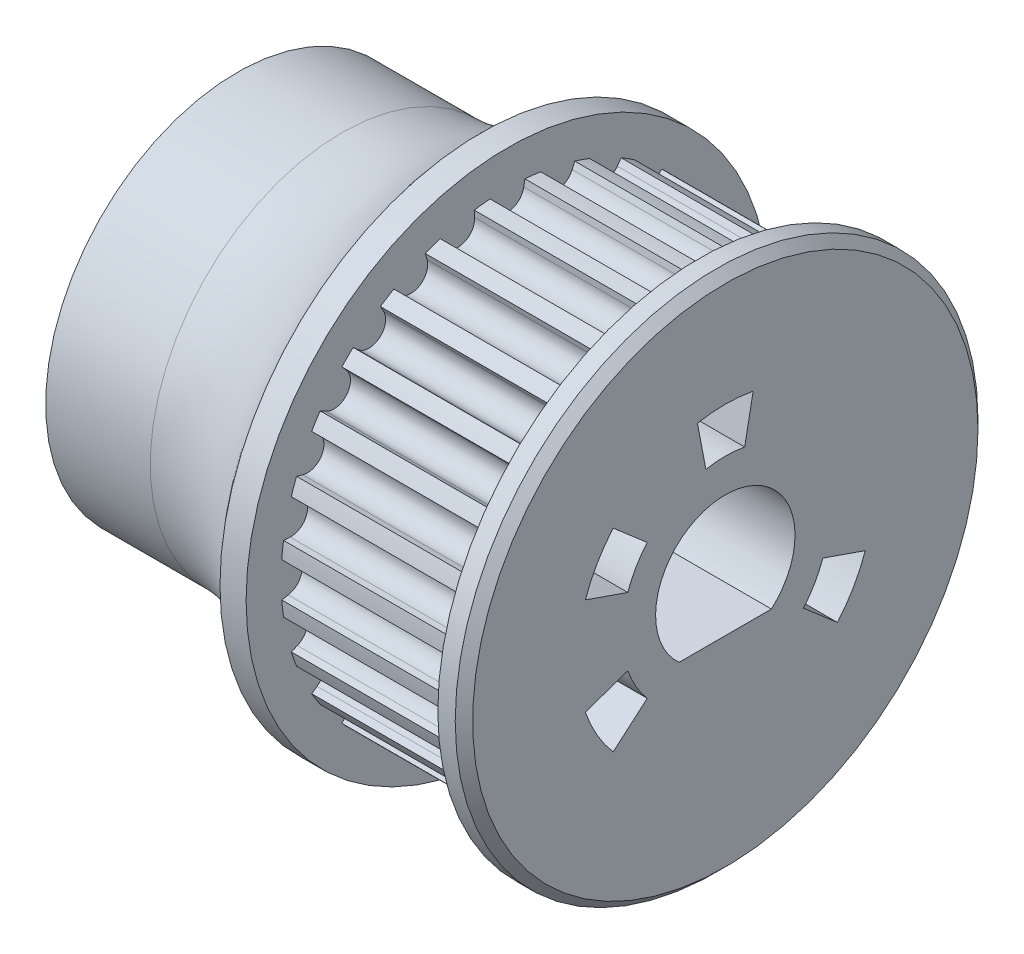
SolidWorks part; units mm, degrees
other "Markup1"
sketch "Sketch8" plane through (-10.5, -15, 15) normal (0, 0, 1) x (1, 0, 0)
material "PLA Density Only"
ref_plane "Front Plane" through (0, 0, 0) normal (0, 0, 1) x (1, 0, 0)
ref_plane "Top Plane" through (0, 0, 0) normal (0, 1, 0) x (1, 0, 0)
ref_plane "Right Plane" through (0, 0, 0) normal (1, 0, 0) x (0, 0, -1)
ref_plane "Plane1" through (-5.5, 0, 0) normal (-1, 0, 0) x (0, -1, 0)
sketch "Sketch5" plane through (0, 0, 0) normal (1, 0, 0) x (0, 0, -1)
  line L0 (1, 12.9515) -> (0.9364, 12.5797)
  line L1 (-0.9364, 12.5797) -> (-1, 12.9515)
  line L2 (-1.907, 12.8493) -> (-1.8863, 12.4727)
  line L3 (-3.7122, 12.056) -> (-3.8569, 12.4042)
  line L4 (-4.7185, 12.1027) -> (-4.6145, 11.7402)
  line L5 (-6.3018, 10.9277) -> (-6.5204, 11.235)
  line L6 (-7.2933, 10.7493) -> (-7.1112, 10.4191)
  line L7 (-8.5754, 9.2514) -> (-8.8569, 9.5024)
  line L8 (-9.5024, 8.8569) -> (-9.2514, 8.5754)
  line L9 (-10.4191, 7.1112) -> (-10.7493, 7.2933)
  line L10 (-11.235, 6.5204) -> (-10.9277, 6.3018)
  line L11 (-11.7402, 4.6145) -> (-12.1027, 4.7185)
  line L12 (-12.4042, 3.8569) -> (-12.056, 3.7122)
  line L13 (-12.4727, 1.8863) -> (-12.8493, 1.907)
  line L14 (-12.9515, 1) -> (-12.5797, 0.9364)
  line L15 (-12.5797, -0.9364) -> (-12.9515, -1)
  line L16 (-12.8493, -1.907) -> (-12.4727, -1.8863)
  line L17 (-12.056, -3.7122) -> (-12.4042, -3.8569)
  line L18 (-12.1027, -4.7185) -> (-11.7402, -4.6145)
  line L19 (-10.9277, -6.3018) -> (-11.235, -6.5204)
  line L20 (-10.7493, -7.2933) -> (-10.4191, -7.1112)
  line L21 (-9.2514, -8.5754) -> (-9.5024, -8.8569)
  line L22 (-8.8569, -9.5024) -> (-8.5754, -9.2514)
  line L23 (-7.1112, -10.4191) -> (-7.2933, -10.7493)
  line L24 (-6.5204, -11.235) -> (-6.3018, -10.9277)
  line L25 (-4.6145, -11.7402) -> (-4.7185, -12.1027)
  line L26 (-3.8569, -12.4042) -> (-3.7122, -12.056)
  line L27 (-1.8863, -12.4727) -> (-1.907, -12.8493)
  line L28 (-1, -12.9515) -> (-0.9364, -12.5797)
  line L29 (0.9364, -12.5797) -> (1, -12.9515)
  line L30 (1.907, -12.8493) -> (1.8863, -12.4727)
  line L31 (3.7122, -12.056) -> (3.8569, -12.4042)
  line L32 (4.7185, -12.1027) -> (4.6145, -11.7402)
  line L33 (6.3018, -10.9277) -> (6.5204, -11.235)
  line L34 (7.2933, -10.7493) -> (7.1112, -10.4191)
  line L35 (8.5754, -9.2514) -> (8.8569, -9.5024)
  line L36 (9.5024, -8.8569) -> (9.2514, -8.5754)
  line L37 (10.4191, -7.1112) -> (10.7493, -7.2933)
  line L38 (11.235, -6.5204) -> (10.9277, -6.3018)
  line L39 (11.7402, -4.6145) -> (12.1027, -4.7185)
  line L40 (12.4042, -3.8569) -> (12.056, -3.7122)
  line L41 (12.4727, -1.8863) -> (12.8493, -1.907)
  line L42 (12.9515, -1) -> (12.5797, -0.9364)
  line L43 (12.5797, 0.9364) -> (12.9515, 1)
  line L44 (12.8493, 1.907) -> (12.4727, 1.8863)
  line L45 (12.056, 3.7122) -> (12.4042, 3.8569)
  line L46 (12.1027, 4.7185) -> (11.7402, 4.6145)
  line L47 (10.9277, 6.3018) -> (11.235, 6.5204)
  line L48 (10.7493, 7.2933) -> (10.4191, 7.1112)
  line L49 (9.2514, 8.5754) -> (9.5024, 8.8569)
  line L50 (8.8569, 9.5024) -> (8.5754, 9.2514)
  line L51 (7.1112, 10.4191) -> (7.2933, 10.7493)
  line L52 (6.5204, 11.235) -> (6.3018, 10.9277)
  line L53 (4.6145, 11.7402) -> (4.7185, 12.1027)
  line L54 (3.8569, 12.4042) -> (3.7122, 12.056)
  line L55 (1.8863, 12.4727) -> (1.907, 12.8493)
  circle A0 centre (0, 0) radius 4
  arc A1 (0.9364, 12.5797) -> (-0.9364, 12.5797) centre (0, 12.74) cw
  arc A2 (-1, 12.9515) -> (-1.907, 12.8493) centre (0, 0) ccw
  arc A3 (-1.8863, 12.4727) -> (-3.7122, 12.056) centre (-2.8349, 12.4206) cw
  arc A4 (-3.8569, 12.4042) -> (-4.7185, 12.1027) centre (0, 0) ccw
  arc A5 (-4.6145, 11.7402) -> (-6.3018, 10.9277) centre (-5.5277, 11.4783) cw
  arc A6 (-6.5204, 11.235) -> (-7.2933, 10.7493) centre (0, 0) ccw
  arc A7 (-7.1112, 10.4191) -> (-8.5754, 9.2514) centre (-7.9433, 9.9605) cw
  arc A8 (-8.8569, 9.5024) -> (-9.5024, 8.8569) centre (0, 0) ccw
  arc A9 (-9.2514, 8.5754) -> (-10.4191, 7.1112) centre (-9.9605, 7.9433) cw
  arc A10 (-10.7493, 7.2933) -> (-11.235, 6.5204) centre (0, 0) ccw
  arc A11 (-10.9277, 6.3018) -> (-11.7402, 4.6145) centre (-11.4783, 5.5277) cw
  arc A12 (-12.1027, 4.7185) -> (-12.4042, 3.8569) centre (0, 0) ccw
  arc A13 (-12.056, 3.7122) -> (-12.4727, 1.8863) centre (-12.4206, 2.8349) cw
  arc A14 (-12.8493, 1.907) -> (-12.9515, 1) centre (0, 0) ccw
  arc A15 (-12.5797, 0.9364) -> (-12.5797, -0.9364) centre (-12.74, 0) cw
  arc A16 (-12.9515, -1) -> (-12.8493, -1.907) centre (0, 0) ccw
  arc A17 (-12.4727, -1.8863) -> (-12.056, -3.7122) centre (-12.4206, -2.8349) cw
  arc A18 (-12.4042, -3.8569) -> (-12.1027, -4.7185) centre (0, 0) ccw
  arc A19 (-11.7402, -4.6145) -> (-10.9277, -6.3018) centre (-11.4783, -5.5277) cw
  arc A20 (-11.235, -6.5204) -> (-10.7493, -7.2933) centre (0, 0) ccw
  arc A21 (-10.4191, -7.1112) -> (-9.2514, -8.5754) centre (-9.9605, -7.9433) cw
  arc A22 (-9.5024, -8.8569) -> (-8.8569, -9.5024) centre (0, 0) ccw
  arc A23 (-8.5754, -9.2514) -> (-7.1112, -10.4191) centre (-7.9433, -9.9605) cw
  arc A24 (-7.2933, -10.7493) -> (-6.5204, -11.235) centre (0, 0) ccw
  arc A25 (-6.3018, -10.9277) -> (-4.6145, -11.7402) centre (-5.5277, -11.4783) cw
  arc A26 (-4.7185, -12.1027) -> (-3.8569, -12.4042) centre (0, 0) ccw
  arc A27 (-3.7122, -12.056) -> (-1.8863, -12.4727) centre (-2.8349, -12.4206) cw
  arc A28 (-1.907, -12.8493) -> (-1, -12.9515) centre (0, 0) ccw
  arc A29 (-0.9364, -12.5797) -> (0.9364, -12.5797) centre (0, -12.74) cw
  arc A30 (1, -12.9515) -> (1.907, -12.8493) centre (0, 0) ccw
  arc A31 (1.8863, -12.4727) -> (3.7122, -12.056) centre (2.8349, -12.4206) cw
  arc A32 (3.8569, -12.4042) -> (4.7185, -12.1027) centre (0, 0) ccw
  arc A33 (4.6145, -11.7402) -> (6.3018, -10.9277) centre (5.5277, -11.4783) cw
  arc A34 (6.5204, -11.235) -> (7.2933, -10.7493) centre (0, 0) ccw
  arc A35 (7.1112, -10.4191) -> (8.5754, -9.2514) centre (7.9433, -9.9605) cw
  arc A36 (8.8569, -9.5024) -> (9.5024, -8.8569) centre (0, 0) ccw
  arc A37 (9.2514, -8.5754) -> (10.4191, -7.1112) centre (9.9605, -7.9433) cw
  arc A38 (10.7493, -7.2933) -> (11.235, -6.5204) centre (0, 0) ccw
  arc A39 (10.9277, -6.3018) -> (11.7402, -4.6145) centre (11.4783, -5.5277) cw
  arc A40 (12.1027, -4.7185) -> (12.4042, -3.8569) centre (0, 0) ccw
  arc A41 (12.056, -3.7122) -> (12.4727, -1.8863) centre (12.4206, -2.8349) cw
  arc A42 (12.8493, -1.907) -> (12.9515, -1) centre (0, 0) ccw
  arc A43 (12.5797, -0.9364) -> (12.5797, 0.9364) centre (12.74, 0) cw
  arc A44 (12.9515, 1) -> (12.8493, 1.907) centre (0, 0) ccw
  arc A45 (12.4727, 1.8863) -> (12.056, 3.7122) centre (12.4206, 2.8349) cw
  arc A46 (12.4042, 3.8569) -> (12.1027, 4.7185) centre (0, 0) ccw
  arc A47 (11.7402, 4.6145) -> (10.9277, 6.3018) centre (11.4783, 5.5277) cw
  arc A48 (11.235, 6.5204) -> (10.7493, 7.2933) centre (0, 0) ccw
  arc A49 (10.4191, 7.1112) -> (9.2514, 8.5754) centre (9.9605, 7.9433) cw
  arc A50 (9.5024, 8.8569) -> (8.8569, 9.5024) centre (0, 0) ccw
  arc A51 (8.5754, 9.2514) -> (7.1112, 10.4191) centre (7.9433, 9.9605) cw
  arc A52 (7.2933, 10.7493) -> (6.5204, 11.235) centre (0, 0) ccw
  arc A53 (6.3018, 10.9277) -> (4.6145, 11.7402) centre (5.5277, 11.4783) cw
  arc A54 (4.7185, 12.1027) -> (3.8569, 12.4042) centre (0, 0) ccw
  arc A55 (3.7122, 12.056) -> (1.8863, 12.4727) centre (2.8349, 12.4206) cw
  arc A56 (1.907, 12.8493) -> (1, 12.9515) centre (0, 0) ccw
extrude "Boss-Extrude2" add sketch "Sketch5" along normal blind 11
sketch "Sketch6" plane through (0, 0, 0) normal (0, 0, 1) x (1, 0, 0)
  line L0 (-5.5, 7) -> (-5.5, 15)
  line L2 (-5.5, 15) -> (-7, 15)
  line L3 (-7, 15) -> (-7, 7)
  line L4 (-7, 7) -> (-21, 7)
  line L5 (-21, 7) -> (-21, 0)
  line L6 (-21, 0) -> (7, 0)
  line L7 (7, 0) -> (7, 15)
  line L8 (7, 15) -> (5.5, 15)
  line L9 (5.5, 15) -> (5.5, 7)
  line L11 (5.5, 7) -> (-5.5, 7)
  dimension "D1" = 1.5
  dimension "D2" = 1.5
  dimension "D3" = 8
  dimension "D6" = 14
  dimension "D7" = 8
ref_axis "Axis1" through (13.9, 0, 0) along (-1, 0, 0)
sketch "Sketch2" plane through (0, 0, 0) normal (0, 0, 1) x (1, 0, 0)
  line L0 (0, 11) -> (0, 15)
  line L1 (-21, 0) -> (7, 0) construction
  line L2 (0, 15) -> (-1.5, 15)
  line L3 (-1.5, 15) -> (-1.5, 11)
  line L4 (-1.5, 11) -> (-15.5, 11)
  line L5 (-15.5, 11) -> (-15.5, 0)
  line L6 (-15.5, 0) -> (12.5, 0)
  line L7 (12.5, 0) -> (12.5, 15)
  line L8 (12.5, 15) -> (11, 15)
  line L9 (11, 15) -> (11, 11)
  line L11 (11, 11) -> (0, 11)
  dimension "D1" = 1.5
  dimension "D2" = 1.5
  dimension "D3" = 15
  dimension "D4" = 11
  dimension "D5" = 11
  dimension "D6" = 14
revolve "Revolve1" add sketch "Sketch2" angle 360 about axis through (13.9, 0, 0) along (-1, 0, 0)
sketch "Sketch3" plane through (-15.5, 0, 0) normal (-1, 0, 0) x (0, 0, 1)
  line L0 (-2.6458, -3) -> (2.6458, -3)
  arc A0 (2.6458, -3) -> (-2.6458, -3) centre (0, 0) ccw
  dimension "D1" = 8
  dimension "D2" = 3
extrude "Cut-Extrude1" cut sketch "Sketch3" against normal through all both and the other way through all
sketch "Sketch7" plane through (-15.5, 0, 0) normal (-1, 0, 0) x (0, 0, 1)
  line L0 (0, 0) -> (0, 15.7922) construction
  line L1 (-1.5978, 8.3521) -> (0, 0) construction
  line L2 (-1.5978, 8.3521) -> (-1.113, 5.8182)
  line L3 (1.113, 5.8182) -> (1.5978, 8.3521)
  line L4 (5.5952, 1.9452) -> (8.032, 2.7923)
  line L5 (6.4342, 5.5597) -> (4.4822, 3.873)
  line L6 (4.4822, -3.873) -> (6.4342, -5.5597)
  line L7 (8.032, -2.7923) -> (5.5952, -1.9452)
  line L10 (-5.5952, -1.9452) -> (-8.032, -2.7923)
  line L11 (-6.4342, -5.5597) -> (-4.4822, -3.873)
  line L14 (-1.113, -5.8182) -> (-1.5978, -8.3521) [skipped]
  line L15 (1.5978, -8.3521) -> (1.113, -5.8182) [skipped]
  line L16 (-4.4822, 3.873) -> (-6.4342, 5.5597) [skipped]
  line L17 (-8.032, 2.7923) -> (-5.5952, 1.9452) [skipped]
  arc A0 (-1.5978, 8.3521) -> (1.5978, 8.3521) centre (0, 0) cw
  arc A1 (-1.113, 5.8182) -> (1.113, 5.8182) centre (0, 0) cw
  arc A2 (6.4342, 5.5597) -> (8.032, 2.7923) centre (0, 0) cw
  arc A3 (4.4822, 3.873) -> (5.5952, 1.9452) centre (0, 0) cw
  arc A4 (8.032, -2.7923) -> (6.4342, -5.5597) centre (0, 0) cw
  arc A5 (5.5952, -1.9452) -> (4.4822, -3.873) centre (0, 0) cw
  arc A8 (-6.4342, -5.5597) -> (-8.032, -2.7923) centre (0, 0) cw
  arc A9 (-4.4822, -3.873) -> (-5.5952, -1.9452) centre (0, 0) cw
  arc A12 (1.5978, -8.3521) -> (-1.5978, -8.3521) centre (0, 0) cw [skipped]
  arc A13 (1.113, -5.8182) -> (-1.113, -5.8182) centre (0, 0) cw [skipped]
  arc A14 (-8.032, 2.7923) -> (-6.4342, 5.5597) centre (0, 0) cw [skipped]
  arc A15 (-5.5952, 1.9452) -> (-4.4822, 3.873) centre (0, 0) cw [skipped]
  point P8 (0, 5.9237)
  point P9 (0, 8.5035)
  dimension "D1" = 6
extrude "Cut-Extrude2" cut sketch "Sketch7" against normal through all
fillet "Fillet1" radius 10 1 edges at (-1.5, 0, -11)
sketch "Sketch9" plane through (0, 0, 0) normal (0, 1, 0) x (1, 0, 0)
  line L0 (13.9, 0) -> (-16.9, 0) construction
  line L1 (-15.5, 11) -> (-15.5, -11) construction
  circle A0 centre (-10.5, 0) radius 2.5
  dimension "D1" = 5
  dimension "D2" = 5
extrude "Cut-Extrude3" cut sketch "Sketch9" against normal through all
ref_plane "Plane2" through (0, 0, 0) normal (0, -0.5, 0.866) x (-1, 0, 0)
sketch "Sketch10" plane through (0, 0, 0) normal (0, -0.5, 0.866) x (-1, 0, 0)
  line L0 (-13.9, 0) -> (16.9, 0) construction
  line L1 (15.5, -11) -> (15.5, 11) construction
  circle A0 centre (10.5, 0) radius 2.5
  dimension "D1" = 5
  dimension "D2" = 5
extrude "Cut-Extrude4" cut sketch "Sketch10" against normal through all
chamfer "Chamfer1" distance 0.5 angle 45 1 edges at (12.5, 0, -15)
